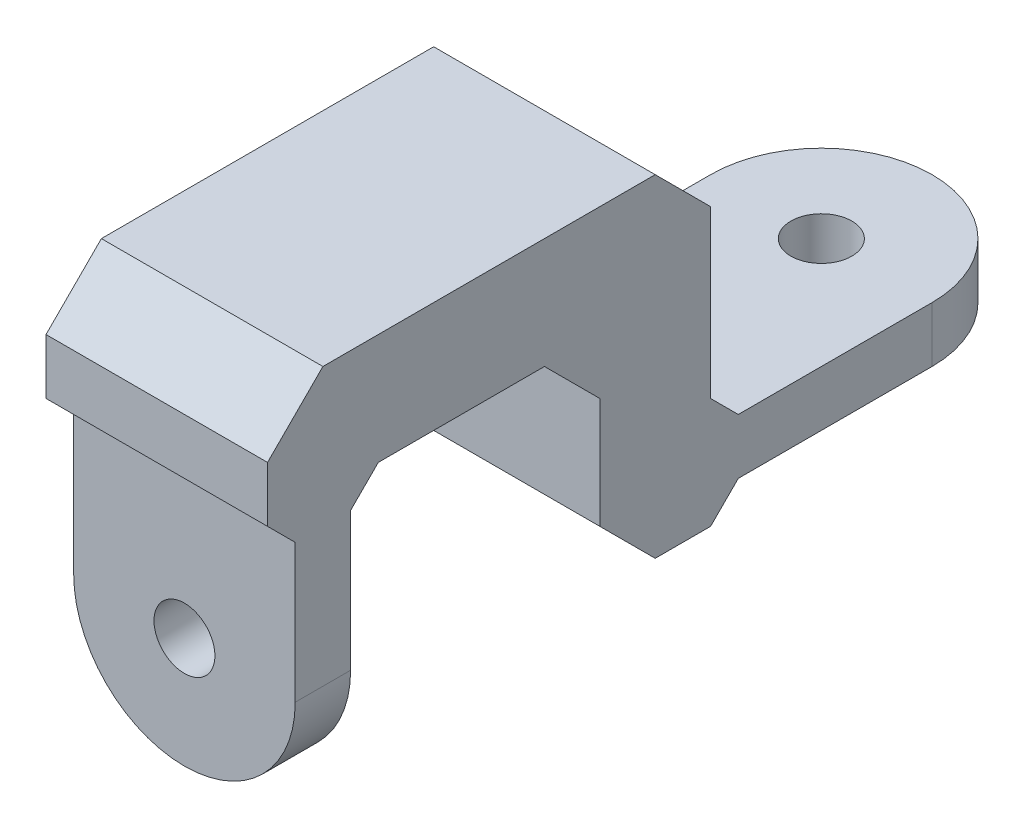
SolidWorks part; units mm, degrees
ref_plane "Front Plane" through (0, 0, 0) normal (0, 0, 1) x (1, 0, 0)
ref_plane "Top Plane" through (0, 0, 0) normal (0, 1, 0) x (1, 0, 0)
ref_plane "Right Plane" through (0, 0, 0) normal (1, 0, 0) x (0, 0, -1)
sketch "Sketch1" plane through (0, 0, 0) normal (0, 0, 1) x (1, 0, 0)
  line L0 (0, -5) -> (0, 5) construction
  line L1 (-10, -5) -> (10, -5)
  line L2 (-10, -5) -> (-10, 5)
  line L3 (-10, 5) -> (10, 5)
  line L4 (10, -5) -> (10, 5)
  dimension "D1" = 10
  dimension "D2" = 20
extrude "Boss-Extrude1" add sketch "Sketch1" along normal blind 10
sketch "Sketch3" plane through (0, 0, 0) normal (0, 0, -1) x (-1, 0, 0)
  line L0 (-10, -5) -> (-10, 5) construction
  line L1 (-10, 2.5) -> (10, 2.5)
  line L2 (-10, 2.5) -> (-10, -2.5)
  line L3 (-10, -2.5) -> (10, -2.5)
  line L4 (10, 2.5) -> (10, -2.5)
  line L5 (10, 5) -> (10, -5) construction
  line L6 (-10, 0) -> (10, 0) construction
  dimension "D1" = 5
extrude "Boss-Extrude2" add sketch "Sketch3" along normal blind 20
fillet "Fillet1" radius 10 2 edges at (-10, 0, -20) (10, 0, -20)
sketch "Sketch4" plane through (-10, 0, 0) normal (-1, 0, 0) x (0, 0, 1)
  line L0 (20, -5) -> (20, 15)
  line L1 (10, -5) -> (20, -5)
  line L2 (10, -5) -> (10, 25)
  line L5 (20, 15) -> (40, 15)
  line L6 (40, 15) -> (40, 10)
  line L7 (40, 10) -> (50, 10)
  line L8 (50, 10) -> (50, 25)
  line L9 (50, 25) -> (10, 25)
  line L10 (0, 0) -> (105.2702, 0) construction
  dimension "D1" = 10
  dimension "D2" = 10
  dimension "D3" = 10
  dimension "D4" = 20
  dimension "D5" = 20
  dimension "D6" = 10
extrude "Boss-Extrude3" add sketch "Sketch4" against normal up to surface (20 mm away) up to face at (10, 0, 0)
sketch "Sketch5" plane through (0, 2.5, 0) normal (0, 1, 0) x (1, 0, 0)
  circle A0 centre (0, 10) radius 2.75
  dimension "D1" = 5.5
extrude "Cut-Extrude1" cut sketch "Sketch5" against normal through all both and the other way through all
chamfer "Chamfer1" distance 10 angle 45 2 edges at (0, 5, 0) (0, -5, 0)
sketch "Sketch6" plane through (0, 10, 0) normal (0, -1, 0) x (1, 0, 0)
  line L0 (-10, 40) -> (-10, 50) construction
  line L1 (-10, 47.5) -> (10, 47.5)
  line L2 (-10, 47.5) -> (-10, 42.5)
  line L3 (-10, 42.5) -> (10, 42.5)
  line L4 (10, 47.5) -> (10, 42.5)
  line L5 (10, 50) -> (10, 40) construction
  line L6 (-10, 45) -> (10, 45) construction
  line L7 (0, 47.5) -> (0, 42.5) construction
  point P12 (0, 45)
  dimension "D1" = 5
extrude "Boss-Extrude4" add sketch "Sketch6" along normal blind 20
fillet "Fillet2" radius 10 2 edges at (10, -10, 45) (-10, -10, 45)
sketch "Sketch7" plane through (0, 0, 47.5) normal (0, 0, 1) x (1, 0, 0)
  circle A0 centre (0, 0) radius 2.75
  arc A1 (0, -10) -> (10, 0) centre (0, 0) ccw construction
  dimension "D1" = 5.5
extrude "Cut-Extrude2" cut sketch "Sketch7" against normal up to surface (5 mm away) and the other way through all up to face at (0, 1.1716, 42.5)
chamfer "Chamfer2" distance 5 angle 45 2 edges at (0, 10, 40) (0, 10, 50)
chamfer "Chamfer3" distance 5 angle 45 4 edges at (0, -5, 20) (0, 15, 20) (0, 25, 10) (0, 25, 50)
